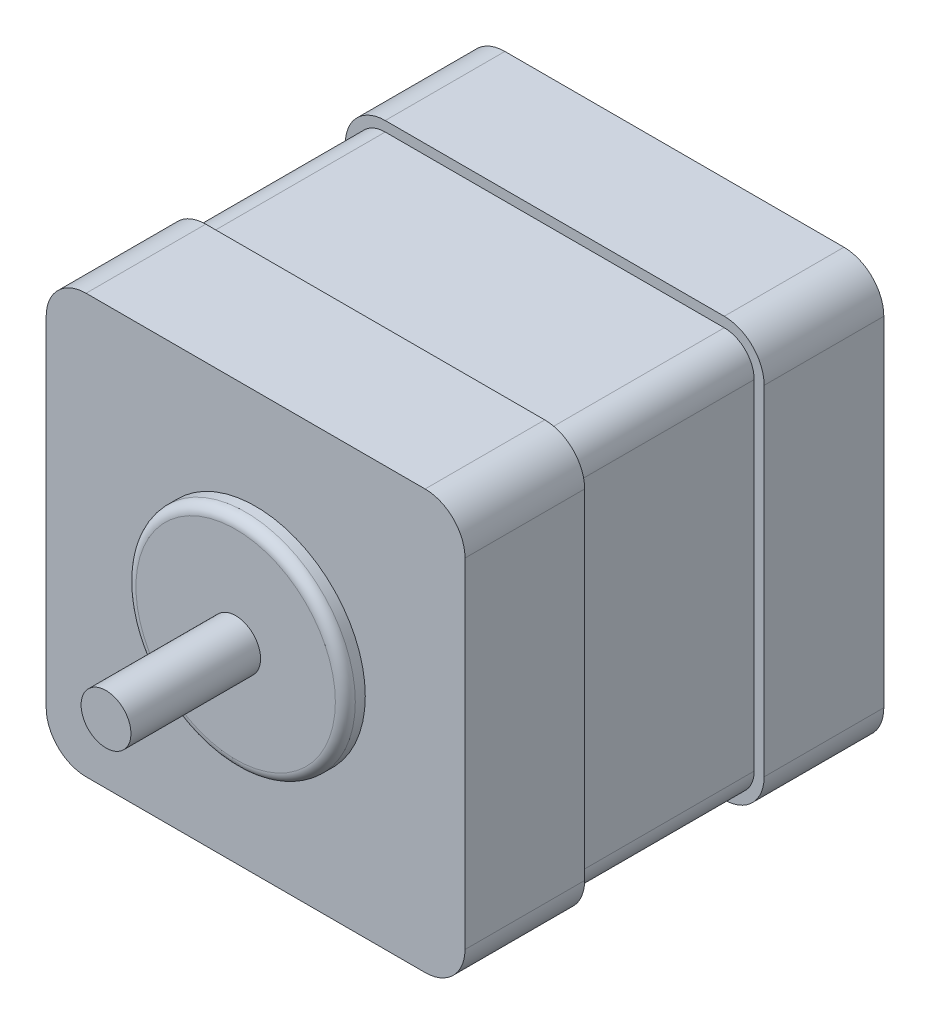
SolidWorks part; units mm, degrees
ref_plane "Front Plane" through (0, 0, 0) normal (0, 0, 1) x (1, 0, 0)
ref_plane "Top Plane" through (0, 0, 0) normal (0, 1, 0) x (1, 0, 0)
ref_plane "Right Plane" through (0, 0, 0) normal (1, 0, 0) x (0, 0, -1)
sketch "Sketch1" plane through (0, 0, 0) normal (0, 0, 1) x (1, 0, 0)
  line L1 (17, -20) -> (-17, -20)
  line L2 (20, -17) -> (20, 17)
  line L3 (17, 20) -> (-17, 20)
  line L4 (-20, -17) -> (-20, 17)
  line L5 (20, -20) -> (-20, 20) construction
  line L6 (20, 20) -> (-20, -20) construction
  arc A0 (-17, -20) -> (-20, -17) centre (-17, -17) cw
  arc A1 (17, -20) -> (20, -17) centre (17, -17) ccw
  arc A2 (20, 17) -> (17, 20) centre (17, 17) ccw
  arc A3 (-17, 20) -> (-20, 17) centre (-17, 17) ccw
  point P0 (0, 0)
  dimension "D3" = 3
  dimension "D1" = 40
  dimension "D2" = 40
extrude "Boss-Extrude1" add sketch "Sketch1" along normal blind 42 contours A3 L3 A2 L2 A1 L1 A0 L4
sketch "Sketch2" plane through (0, 0, 42) normal (0, 0, 1) x (1, 0, 0)
  circle A0 centre (0, 0) radius 11
  dimension "D1" = 22
extrude "Boss-Extrude2" add sketch "Sketch2" along normal blind 2 contours A0
fillet "Fillet1" radius 1 1 edges at (11, 0, 44)
sketch "Sketch3" plane through (0, 0, 44) normal (0, 0, 1) x (1, 0, 0)
  circle A0 centre (0, 0) radius 2.5
  dimension "D1" = 5
extrude "Boss-Extrude3" add sketch "Sketch3" along normal blind 13
sketch "Sketch4" plane through (0, 0, 42) normal (0, 0, 1) x (1, 0, 0)
  line L12 (-19, 18) -> (-19, -18)
  line L13 (-18, -19) -> (18, -19)
  line L14 (19, -18) -> (19, 18)
  line L15 (18, 19) -> (-18, 19)
  arc A12 (-19, -18) -> (-18, -19) centre (-18, -18) ccw
  arc A13 (18, -19) -> (19, -18) centre (18, -18) ccw
  arc A14 (19, 18) -> (18, 19) centre (18, 18) ccw
  arc A15 (-18, 19) -> (-19, 18) centre (-18, 18) ccw
  circle M9 centre (0, 0) radius 11
  line M10 (-20, 17) -> (-20, -17)
  arc M11 (-20, -17) -> (-17, -20) centre (-17, -17) ccw
  line M12 (-17, -20) -> (17, -20)
  arc M13 (17, -20) -> (20, -17) centre (17, -17) ccw
  line M14 (20, -17) -> (20, 17)
  arc M15 (20, 17) -> (17, 20) centre (17, 17) ccw
  line M16 (17, 20) -> (-17, 20)
  arc M17 (-17, 20) -> (-20, 17) centre (-17, 17) ccw
extrude "Cut-Extrude5" cut sketch "Sketch4" against normal blind 12 from offset 6 flip side to cut contours A15 L15 A14 L14 A13 L13 A12 L12 M17 M10 M11 M12 M13 M14 M15 M16 | L15 A15 L12 A12 L13 A13 L14 A14 M9 region at (-18.3271, 18.3271, 42) region at (-18.7213, 18.7213, 42) offset against normal yes
sketch "Sketch5" plane through (0, 0, 42) normal (0, 0, 1) x (1, 0, 0)
  line L9 (-21, 17) -> (-21, -17)
  line L10 (-17, -21) -> (17, -21)
  line L11 (21, -17) -> (21, 17)
  line L12 (17, 21) -> (-17, 21)
  line L13 (-21, 17) -> (-21, -17)
  line L14 (-17, -21) -> (17, -21)
  line L15 (21, -17) -> (21, 17)
  line L16 (17, 21) -> (-17, 21)
  arc A8 (-21, -17) -> (-17, -21) centre (-17, -17) ccw
  arc A9 (17, -21) -> (21, -17) centre (17, -17) ccw
  arc A10 (21, 17) -> (17, 21) centre (17, 17) ccw
  arc A11 (-17, 21) -> (-21, 17) centre (-17, 17) ccw
  arc A12 (-21, -17) -> (-17, -21) centre (-17, -17) ccw
  arc A13 (17, -21) -> (21, -17) centre (17, -17) ccw
  arc A14 (21, 17) -> (17, 21) centre (17, 17) ccw
  arc A15 (-17, 21) -> (-21, 17) centre (-17, 17) ccw
  dimension "D1" = 1
extrude "Boss-Extrude4" add sketch "Sketch5" against normal blind 12 contours L13 A12 L14 A13 L15 A14 L16 A15
sketch "Sketch6" plane through (0, 0, 0) normal (0, 0, -1) x (-1, 0, 0)
  line L8 (21, -17) -> (21, 17)
  line L9 (17, 21) -> (-17, 21)
  line L10 (-21, 17) -> (-21, -17)
  line L11 (-17, -21) -> (17, -21)
  line L12 (21, -17) -> (21, 17)
  line L13 (17, 21) -> (-17, 21)
  line L14 (-21, 17) -> (-21, -17)
  line L15 (-17, -21) -> (17, -21)
  arc A8 (21, 17) -> (17, 21) centre (17, 17) ccw
  arc A9 (-17, 21) -> (-21, 17) centre (-17, 17) ccw
  arc A10 (-21, -17) -> (-17, -21) centre (-17, -17) ccw
  arc A11 (17, -21) -> (21, -17) centre (17, -17) ccw
  arc A12 (21, 17) -> (17, 21) centre (17, 17) ccw
  arc A13 (-17, 21) -> (-21, 17) centre (-17, 17) ccw
  arc A14 (-21, -17) -> (-17, -21) centre (-17, -17) ccw
  arc A15 (17, -21) -> (21, -17) centre (17, -17) ccw
  dimension "D1" = 1
extrude "Boss-Extrude5" add sketch "Sketch6" against normal blind 12 contours L12 A12 L13 A13 L14 A14 L15 A15
